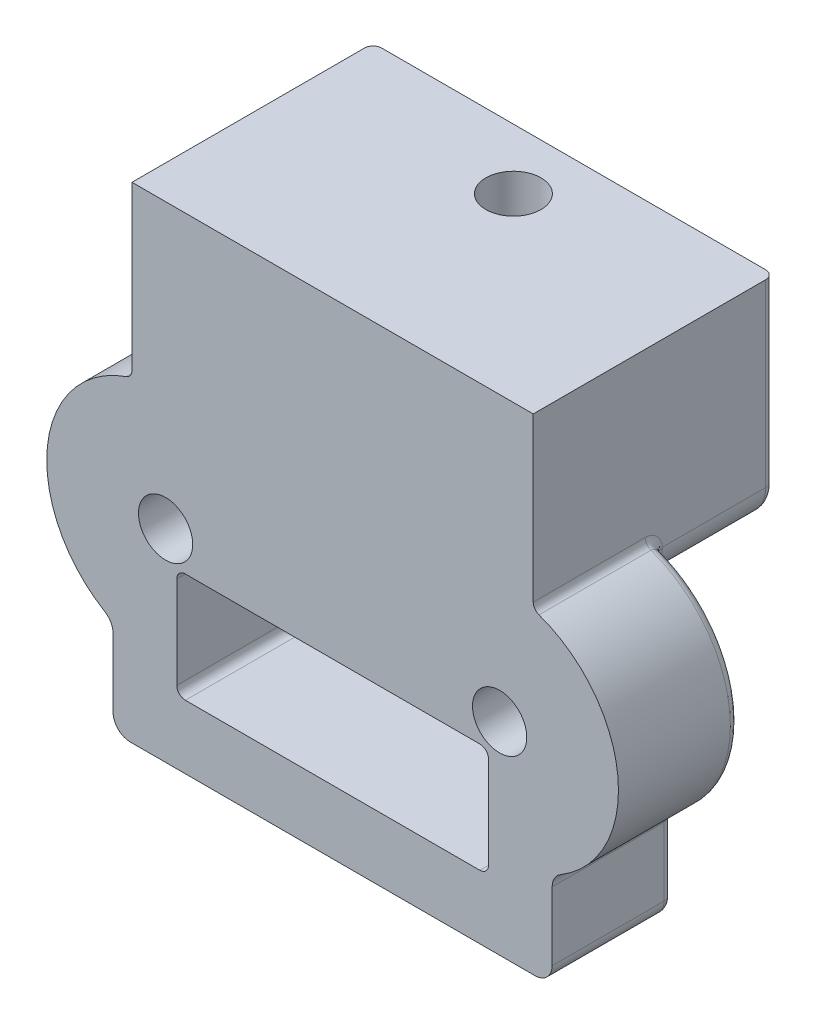
SolidWorks part; units mm, degrees
ref_plane "Спереди" through (0, 0, 0) normal (0, 0, 1) x (1, 0, 0)
ref_plane "Сверху" through (0, 0, 0) normal (0, 1, 0) x (1, 0, 0)
ref_plane "Справа" through (0, 0, 0) normal (1, 0, 0) x (0, 0, -1)
sketch "Эскиз5" plane through (0, 0, 0) normal (0, 0, 1) x (1, 0, 0)
  line L0 (7.65, 0) -> (-7.65, 0) construction
  line L1 (-7.65, 0) -> (-7.65, -1.75) construction
  line L2 (-9.7, -2.55) -> (-8.45, -2.55) construction
  line L3 (-9.7, -8.35) -> (-8.45, -8.35) construction
  line L4 (-8.75, -8.15) -> (-8.75, -9.25) construction
  line L5 (-8.75, -9.25) -> (-8.75, -13.2) construction
  line L6 (8.75, -13.2) -> (-8.75, -13.2) construction
  line L7 (8.75, -9.25) -> (8.75, -8.15) construction
  line L8 (8.75, -9.25) -> (8.75, -13.2) construction
  line L9 (9.7, -8.35) -> (8.45, -8.35) construction
  line L10 (9.7, -2.55) -> (8.45, -2.55) construction
  line L11 (7.65, -1.75) -> (7.65, 0) construction
  line L12 (7.65, 0) -> (-7.65, 0) construction
  line L13 (-7.65, 0) -> (-7.65, -1.75) construction
  line L14 (-9.7, -2.55) -> (-8.45, -2.55) construction
  line L15 (-9.7, -8.35) -> (-8.45, -8.35) construction
  line L16 (-8.75, -8.15) -> (-8.75, -9.25) construction
  line L17 (-8.75, -9.25) -> (-8.75, -13.2) construction
  line L18 (8.75, -13.2) -> (-8.75, -13.2) construction
  line L19 (8.75, -9.25) -> (8.75, -8.15) construction
  line L20 (8.75, -9.25) -> (8.75, -13.2) construction
  line L21 (9.7, -8.35) -> (8.45, -8.35) construction
  line L22 (9.7, -2.55) -> (8.45, -2.55) construction
  line L23 (7.65, -1.75) -> (7.65, 0) construction
  line L25 (11.65, 1.1687) -> (11.65, 1.1687)
  line L26 (11.65, 1.1687) -> (11.65, 4)
  line L27 (11.65, 4) -> (-11.65, 4)
  line L28 (-11.65, 4) -> (-11.65, 1.1687)
  line L29 (-11.65, 1.1687) -> (-11.65, 1.1687)
  line L30 (12.75, -9.25) -> (12.75, -17.2) construction
  line L31 (-12.75, -9.25) -> (-12.75, -17.2) construction
  line L32 (-12.75, -11.6393) -> (-12.75, -17.2)
  line L33 (12.75, -17.2) -> (-12.75, -17.2)
  line L34 (12.75, -11.6393) -> (12.75, -17.2)
  line L36 (12.75, -9.25) -> (12.75, -8.15) construction
  line L37 (9.7, -12.35) -> (8.45, -12.35) construction
  line L38 (-9.7, -12.35) -> (-8.45, -12.35) construction
  line L39 (-12.75, -8.15) -> (-12.75, -9.25) construction
  arc A0 (-8.45, -2.55) -> (-7.65, -1.75) centre (-8.45, -1.75) ccw construction
  arc A1 (-9.7, -2.55) -> (-9.7, -8.35) centre (-9.7, -5.45) ccw construction
  arc A2 (9.7, -8.35) -> (9.7, -2.55) centre (9.7, -5.45) ccw construction
  arc A3 (7.65, -1.75) -> (8.45, -2.55) centre (8.45, -1.75) ccw construction
  arc A4 (-8.45, -2.55) -> (-7.65, -1.75) centre (-8.45, -1.75) ccw construction
  arc A5 (-9.7, -2.55) -> (-9.7, -8.35) centre (-9.7, -5.45) ccw construction
  arc A6 (9.7, -8.35) -> (9.7, -2.55) centre (9.7, -5.45) ccw construction
  arc A7 (7.65, -1.75) -> (8.45, -2.55) centre (8.45, -1.75) ccw construction
  arc A8 (12.75, -11.6393) -> (11.65, 1.1687) centre (9.7, -5.45) ccw
  arc A9 (11.65, 1.1687) -> (11.65, 1.1687) centre (11.65, 1.1687) ccw
  arc A10 (-11.65, 1.1687) -> (-11.65, 1.1687) centre (-11.65, 1.1687) ccw
  arc A11 (-11.65, 1.1687) -> (-12.75, -11.6393) centre (-9.7, -5.45) ccw
  arc A13 (9.7, -12.35) -> (11.65, 1.1687) centre (9.7, -5.45) ccw construction
  arc A14 (-11.65, 1.1687) -> (-9.7, -12.35) centre (-9.7, -5.45) ccw construction
  dimension "D1" = 4
extrude "Бобышка-Вытянуть2" add sketch "Эскиз5" against normal up to surface (7 mm away)
hole_wizard "Сверло под метчик  спиральное M31" positions "Эскиз6" profile "Эскиз8" hole size "M3x0.5" standard "DIN" end condition through all
sketch "Эскиз6" plane through (0, 0, -7) normal (0, 0, -1) x (-1, 0, 0)
  point P0 (-9.7, -5.45)
  point P3 (9.7, -5.45)
sketch "Эскиз8" plane through (9.7, -5.45, -7) normal (1, 0, 0) x (0, 1, 0)
  line L0 (0, 0) -> (0, 7)
  line L1 (0, 7) -> (1.575, 7)
  line L2 (1.575, 7) -> (1.575, 0)
  line L5 (1.575, 0) -> (0, 0)
  line L11 (0, -6.35) -> (0, 107.95) construction
  dimension "Диаметр сквозного отверстия" = 3.15
  dimension "Глубина сквозного отверстия" = 7
sketch "Эскиз9" plane through (0, 0, -7) normal (0, 0, -1) x (-1, 0, 0)
  line L0 (8.75, -9.25) -> (8.75, -13.2) construction
  line L1 (-8.75, -9.25) -> (-8.75, -13.2) construction
  line L2 (-8.75, -13.2) -> (8.75, -13.2) construction
  line L3 (5, -7.45) -> (-5, -7.45) construction
  line L4 (8.75, -9.25) -> (8.75, -13.2) construction
  line L5 (-8.75, -9.25) -> (-8.75, -13.2) construction
  line L6 (-8.75, -13.2) -> (8.75, -13.2) construction
  line L7 (5, -7.45) -> (-5, -7.45) construction
  line L8 (-8.75, -9.25) -> (-8.75, -7.45) construction
  line L10 (-5, -7.45) -> (-8.75, -7.45) construction
  line L12 (5, -7.45) -> (8.75, -7.45) construction
  line L13 (8.75, -9.25) -> (8.75, -7.45) construction
  line L14 (-8.75, -7.45) -> (8.75, -13.2) construction
  line L15 (-8.75, -13.2) -> (8.75, -7.45) construction
  line L17 (-9.05, -13.5) -> (9.05, -13.5)
  line L18 (-9.05, -13.5) -> (-9.05, -7.15)
  line L19 (-9.05, -7.15) -> (9.05, -7.15)
  line L20 (9.05, -13.5) -> (9.05, -7.15)
  line L21 (-9.05, -13.5) -> (9.05, -7.15) construction
  line L22 (-9.05, -7.15) -> (9.05, -13.5) construction
  point P8 (0, -10.325)
  dimension "D1" = 0.3
  dimension "D2" = 0.3
extrude "Вырез-Вытянуть1" cut sketch "Эскиз9" against normal through all
fillet "Скругление3" radius 0.5 4 edges at (-9.05, -7.15, -3.5) (9.05, -7.15, -3.5) (-9.05, -13.5, -3.5) (9.05, -13.5, -3.5)
sketch "Эскиз10" plane through (0, 0, -7) normal (0, 0, -1) x (-1, 0, 0)
  line L0 (11.65, 4) -> (11.65, 1.1687) construction
  line L1 (-11.65, 1.1687) -> (-11.65, 4) construction
  line L2 (-11.65, 4) -> (11.65, 4) construction
  line L3 (11.65, 4) -> (11.65, 1.1687) construction
  line L4 (-11.65, 1.1687) -> (-11.65, 4) construction
  line L5 (-11.65, 4) -> (11.65, 4) construction
  line L7 (-11.65, -4) -> (11.65, -4)
  line L8 (-11.65, -4) -> (-11.65, 4)
  line L9 (-11.65, 4) -> (11.65, 4)
  line L10 (11.65, -4) -> (11.65, 4)
  line L11 (-11.65, -4) -> (11.65, 4) construction
  line L12 (-11.65, 4) -> (11.65, -4) construction
  line L13 (8.55, -7.15) -> (-8.55, -7.15) construction
  line L14 (8.55, -7.15) -> (-8.55, -7.15) construction
  point P6 (0, 0)
  dimension "D1" = 8
extrude "Бобышка-Вытянуть3" add sketch "Эскиз10" along normal blind 7
sketch "Эскиз14" plane through (0, 0, -14) normal (0, 0, -1) x (-1, 0, 0)
  circle A0 centre (-9.7, -5.45) radius 4
  circle A1 centre (9.7, -5.45) radius 4
  dimension "D1" = 8
extrude "Вырез-Вытянуть4" cut sketch "Эскиз14" against normal up to surface (7 mm away) up to face at (0, -7.0533, -7)
fillet "Скругление9" radius 2 4 edges at (11.65, -1.9575, -10.5) (-11.65, -1.9575, -10.5) (-5.9721, -4, -10.5) (5.9721, -4, -10.5)
fillet "Скругление10" radius 0.5 23 edges at (11.65, 1.1687, -3.5) (-11.65, 1.1687, -3.5) (11.0701, -0.8585, -7) (7.8413, -1.9081, -7) (-7.8413, -1.9081, -7) (11.65, 2.2749, -14) (11.0701, -0.8585, -14) (7.8413, -1.9081, -14) (0, -4, -14) (-7.8413, -1.9081, -14) (-11.0701, -0.8585, -14) (12.75, -14.4197, -7) (0, -17.2, -7) (-12.75, -14.4197, -7) (-16.5747, -4.8596, -7) (16.5747, -4.8596, -7) (-11.0701, -0.8585, -7) (-11.65, 2.2749, -14) (5.713, -3.7748, -7) (0, -4, -7) (-5.713, -3.7748, -7) (5.713, -3.7748, -14) (-5.713, -3.7748, -14)
fillet "Скругление11" radius 1 8 edges at (-12.6663, -11.587, -6.777) (-12.6036, -17.0536, -6.8536) (12.6036, -17.0536, -6.8536) (12.6663, -11.587, -6.777) (-12.75, -11.6393, -3.25) (-12.75, -17.2, -3.25) (12.75, -17.2, -3.25) (12.75, -11.6393, -3.25)
sketch "Эскиз18" plane through (0, 4, 0) normal (0, 1, 0) x (1, 0, 0)
  line L4 (11.65, 0) -> (11.65, 13.5)
  line L5 (11.15, 14) -> (-11.15, 14)
  line L6 (-11.65, 13.5) -> (-11.65, 0)
  line L7 (-11.65, 0) -> (11.65, 0)
  line L8 (11.65, 0) -> (11.65, 13.5)
  line L9 (11.15, 14) -> (-11.15, 14)
  line L10 (-11.65, 13.5) -> (-11.65, 0)
  line L11 (-11.65, 0) -> (11.65, 0)
  arc A2 (11.65, 13.5) -> (11.15, 14) centre (11.15, 13.5) ccw
  arc A3 (-11.15, 14) -> (-11.65, 13.5) centre (-11.15, 13.5) ccw
  arc A4 (11.65, 13.5) -> (11.15, 14) centre (11.15, 13.5) ccw
  arc A5 (-11.15, 14) -> (-11.65, 13.5) centre (-11.15, 13.5) ccw
  dimension "D1" = 0
extrude "Бобышка-Вытянуть4" add sketch "Эскиз18" along normal blind 7
hole_wizard "Отверстие с зазором M31" positions "Эскиз16" profile "Эскиз17" hole size "M3" standard "DIN" end condition through all
sketch "Эскиз16" plane through (0, -7.15, 0) normal (0, -1, 0) x (-1, 0, 0)
  line L4 (-4.7911, 10.5) -> (4.7911, 10.5) construction
  line L5 (-4.7911, 13.5) -> (-4.7911, 7.5) construction
  line L6 (4.7911, 7.5) -> (4.7911, 13.5) construction
  point P24 (0, 10.5)
sketch "Эскиз17" plane through (0, -7.15, -10.5) normal (1, 0, 0) x (0, 0, -1)
  line L0 (0, 0) -> (0, 18.15)
  line L1 (0, 18.15) -> (1.6, 18.15)
  line L2 (1.6, 18.15) -> (1.6, 0)
  line L5 (1.6, 0) -> (0, 0)
  line L11 (0, -6.35) -> (0, 107.95) construction
  dimension "Диаметр сквозного отверстия" = 3.2
  dimension "Глубина сквозного отверстия" = 18.15
